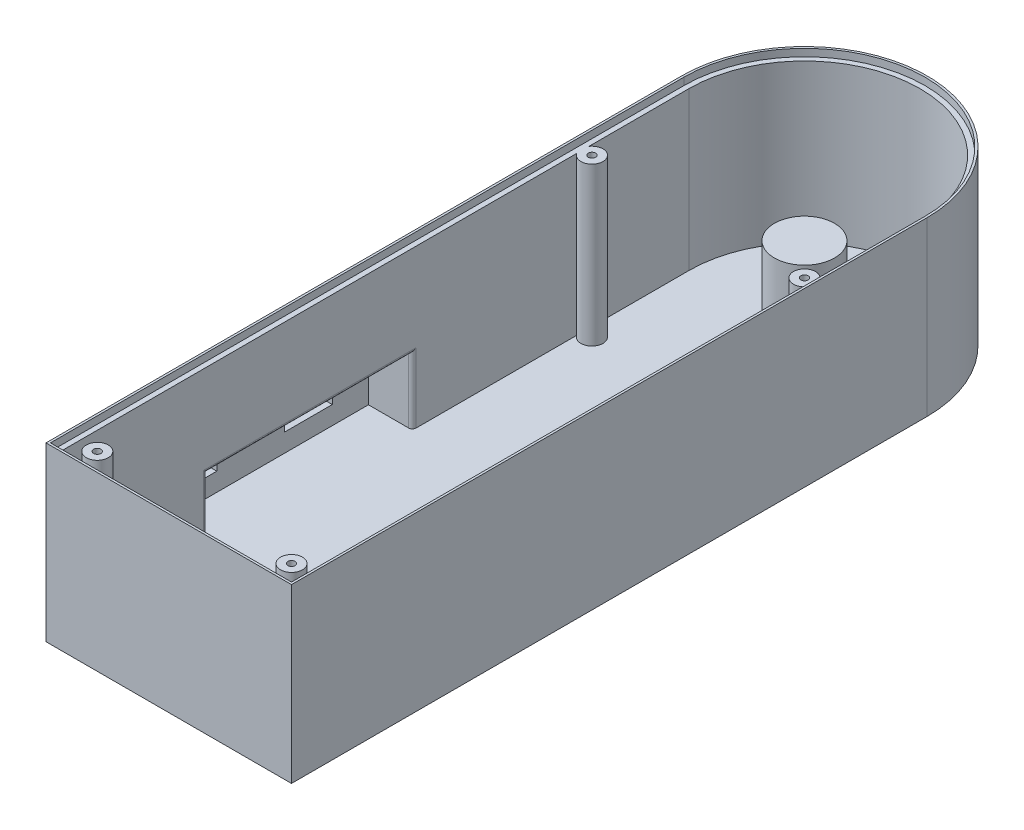
SolidWorks part; units mm, degrees
ref_plane "Front Plane" through (0, 0, 0) normal (0, 0, 1) x (1, 0, 0)
ref_plane "Top Plane" through (0, 0, 0) normal (0, 1, 0) x (1, 0, 0)
ref_plane "Right Plane" through (0, 0, 0) normal (1, 0, 0) x (0, 0, -1)
sketch "Sketch1" plane through (0, 0, 0) normal (0, 0, 1) x (1, 0, 0)
  line L6 (0, 0) -> (0, 47) construction
  line L8 (-31.5, 48) -> (-31.5, 50)
  line L9 (-31.5, 50) -> (-33.5, 50)
  line L10 (-33.5, 50) -> (-33.5, 0)
  line L11 (-33.5, 0) -> (0, 0)
  line L13 (0, 24.8) -> (-8.2, 24.8)
  line L14 (-31.5, 2) -> (-8.2, 2)
  line L17 (-31.5, 45) -> (-31.5, 2)
  line L18 (-8.2, 2) -> (-8.2, 24.8)
  line L19 (0, 0) -> (0, 24.8)
  line L20 (-4, 48) -> (-4, 45)
  line L23 (-31.5, 48) -> (-4, 48)
  line L24 (-31.5, 45) -> (-4, 45)
  dimension "D1" = 33.5
  dimension "D2" = 8
  dimension "D3" = 2
  dimension "D4" = 50
  dimension "D5" = 3
  dimension "D6" = 8.2
  dimension "D7" = 2
  dimension "D8" = 2
  dimension "D9" = 24.8
revolve "Revolve1" add sketch "Sketch1" angle 360 about L6
sketch "Sketch4" plane through (0, 0, 0) normal (0, 0, 1) x (1, 0, 0)
  line L3 (33.5, 0) -> (-33.5, 0)
  line L4 (-31.5, 45) -> (-31.5, 2)
  line L5 (-31.5, 2) -> (31.5, 2)
  line L6 (31.5, 2) -> (31.5, 45)
  line L7 (31.5, 45) -> (-31.5, 45)
  line L8 (31.5, 48) -> (33.5, 48)
  line L9 (-31.5, 48) -> (31.5, 48)
  line L10 (33.5, 48) -> (33.5, 0)
  line L11 (-31.5, 48) -> (-33.5, 48)
  line L12 (-33.5, 48) -> (-33.5, 0)
  dimension "D4" = 2
extrude "Boss-Extrude2" add sketch "Sketch4" along normal blind 173.5
sketch "Sketch6" plane through (0, 48, 0) normal (0, 1, 0) x (1, 0, 0)
  line L0 (4, 0) -> (-4, 0) construction
  circle A0 centre (0, 0) radius 4
extrude "Cut-Extrude1" cut sketch "Sketch6" against normal blind 3
sketch "Sketch9" plane through (0, 0, 173.5) normal (0, 0, 1) x (1, 0, 0)
  line L0 (-31.5, 45) -> (-31.5, 2)
  line L1 (-31.5, 2) -> (31.5, 2)
  line L2 (31.5, 2) -> (31.5, 45)
  line L3 (31.5, 45) -> (-31.5, 45)
extrude "Cut-Extrude2" cut sketch "Sketch9" against normal blind 173.5
sketch "Sketch10" plane through (0, 2, 0) normal (0, 1, 0) x (1, 0, 0)
  line L0 (-8.2, 0) -> (8.2, 0) construction
  circle A0 centre (0, 0) radius 8.2
extrude "Boss-Extrude3" add sketch "Sketch10" along normal blind 22.8
sketch "Sketch11" plane through (0, 0, 173.5) normal (0, 0, 1) x (1, 0, 0)
  line L1 (-31.5, 2) -> (31.5, 2)
  line L2 (-31.5, 2) -> (-31.5, 45)
  line L3 (-31.5, 45) -> (31.5, 45)
  line L4 (31.5, 2) -> (31.5, 45)
extrude "Boss-Extrude4" add sketch "Sketch11" against normal blind 2
sketch "Sketch13" plane through (0, 2, 0) normal (0, 1, 0) x (1, 0, 0)
  line L0 (-26.5, -161.5) -> (-26.5, -171.5)
  line L1 (-31.5, -171.5) -> (-21.5, -171.5)
  line L2 (-31.5, -171.5) -> (-31.5, -161.5)
  line L3 (-31.5, -161.5) -> (-21.5, -161.5)
  line L4 (-21.5, -171.5) -> (-21.5, -161.5)
  line L5 (31.5, -171.5) -> (21.5, -171.5)
  line L6 (31.5, -171.5) -> (31.5, -161.5)
  line L7 (31.5, -161.5) -> (21.5, -161.5)
  line L8 (21.5, -171.5) -> (21.5, -161.5)
  line L9 (-26.5, -171.5) -> (-21.5, -166.5)
  line L10 (-21.5, -166.5) -> (-31.5, -166.5)
  line L11 (26.5, -161.5) -> (26.5, -171.5)
  line L12 (26.5, -171.5) -> (21.5, -166.5)
  line L13 (21.5, -166.5) -> (31.5, -166.5)
  circle A0 centre (-26.5, -166.5) radius 3
  circle A1 centre (26.5, -166.5) radius 3
  dimension "D1" = 10
  dimension "D2" = 10
  dimension "D3" = 10
extrude "Boss-Extrude5" add sketch "Sketch13" along normal blind 43 contours A0 | A1
sketch "Sketch14" plane through (0, 2, 0) normal (0, 1, 0) x (1, 0, 0)
  circle A0 centre (-26.5, -166.5) radius 1
  circle A1 centre (26.5, -166.5) radius 1
extrude "Cut-Extrude3" cut sketch "Sketch14" along normal blind 46
sketch "Sketch15" plane through (0, 48, 0) normal (0, 1, 0) x (1, 0, 0)
  circle A0 centre (-26.5, -166.5) radius 4.3
  circle A1 centre (26.5, -166.5) radius 4.3
extrude "Cut-Extrude4" cut sketch "Sketch15" against normal blind 2
fillet "Fillet1" radius 1 2 edges at (26.5, 46, 170.8) (-26.5, 46, 170.8)
sketch "Sketch16" plane through (0, 48, 0) normal (0, 1, 0) x (1, 0, 0)
  line L0 (0, -173.5) -> (0, -33.5)
  line L1 (33.5, -173.5) -> (-33.5, -173.5) construction
  line L2 (0, -103.5) -> (-33.5, -103.5)
  line L3 (-33.5, -173.5) -> (-33.5, 0) construction
  line L4 (0, -103.5) -> (0, -150.5)
  line L5 (-29.9, -148.5) -> (-3.6, -148.5)
  line L6 (-29.9, -148.5) -> (-29.9, -58.5)
  line L7 (-29.9, -58.5) -> (-3.6, -58.5)
  line L8 (-3.6, -148.5) -> (-3.6, -58.5)
  line L9 (-29.9, -148.5) -> (-3.6, -58.5) construction
  line L10 (-29.9, -58.5) -> (-3.6, -148.5) construction
  line L11 (0, -150.5) -> (-33.5, -150.5)
  line L12 (-33.5, -150.5) -> (-33.5, -56.5)
  line L13 (-33.5, -56.5) -> (0, -56.5)
  line L14 (0, -56.5) -> (0, -103.5)
  arc A0 (-33.5, 0) -> (33.5, 0) centre (0, 0) ccw construction
  point P11 (-16.75, -103.5)
  dimension "D1" = 90
  dimension "D2" = 26.3
  dimension "D3" = 2
  dimension "D4" = 2
sketch "Sketch19" plane through (0, 48, 0) normal (0, 1, 0) x (1, 0, 0)
  line L0 (0, -173.5) -> (0, -33.5) construction
  line L1 (0, -173.5) -> (0, -33.5)
  line L2 (0, -103.5) -> (33.5, -103.5)
  line L3 (33.5, -173.5) -> (33.5, 0) construction
  line L4 (33.5, -103.5) -> (16.75, -103.5)
  line L5 (16.75, -103.5) -> (16.75, -68.5)
  line L7 (16.75, -68.5) -> (16.75, -33.5)
  line L8 (0, -68.5) -> (33.5, -68.5)
  line L9 (0, -138.5) -> (33.5, -138.5)
  line L10 (16.75, -103.5) -> (16.75, -138.5)
  line L11 (16.75, -138.5) -> (16.75, -173.5)
  line L12 (33.5, -173.5) -> (-33.5, -173.5) construction
  circle A0 centre (16.75, -51) radius 6
  circle A1 centre (16.75, -86) radius 6
  circle A2 centre (16.75, -121) radius 6
  circle A3 centre (16.75, -156) radius 6
extrude "Cut-Extrude5" cut sketch "Sketch19" against normal blind 3 contours A0 | A1 | A2 | A3
ref_plane "Plane2" through (0, 0, 56.5) normal (0, 0, 1) x (1, 0, 0)
sketch "Sketch20" plane through (0, 0, 56.5) normal (0, 0, 1) x (1, 0, 0)
  line L0 (9, 48) -> (-11.2073, 83)
  line L1 (0, 48) -> (-33.5, 48) construction
  line L3 (-33.5, 48) -> (9, 48)
  line L5 (5.5359, 50) -> (-12.362, 81)
  line L7 (-31.5, 50) -> (5.5359, 50)
  line L8 (-33.5, 48) -> (-33.5, 0) construction
  line L11 (-33.5, 48) -> (-33.5, 83)
  line L12 (-33.5, 83) -> (-11.2073, 83)
  line L13 (-31.5, 50) -> (-31.5, 81)
  line L14 (-31.5, 81) -> (-12.362, 81)
  dimension "D1" = 60
  dimension "D3" = 2
  dimension "D4" = 2
  dimension "D2" = 2
  dimension "D5" = 2
  dimension "D6" = 9
  dimension "D7" = 35
extrude "Boss-Extrude6" add sketch "Sketch20" along normal up to vertex (94 mm away) up to point (-33.5, 48, 150.5)
sketch "Sketch21" plane through (0, 50, 0) normal (0, 1, 0) x (1, 0, 0)
  line L1 (-31.5, -150.5) -> (5.5359, -150.5)
  line L2 (-31.5, -150.5) -> (-31.5, -56.5)
  line L3 (-31.5, -56.5) -> (5.5359, -56.5)
  line L4 (5.5359, -150.5) -> (5.5359, -56.5)
extrude "Cut-Extrude6" cut sketch "Sketch21" against normal blind 13
fillet "Fillet2" radius 1 2 edges at (-11.2073, 83, 103.5) (-33.5, 83, 103.5)
sketch "Sketch22" plane through (0, 0, 150.5) normal (0, 0, 1) x (1, 0, 0)
  line L1 (-33.5, 48) -> (-33.5, 45)
  line L2 (-33.5, 45) -> (9, 45)
  line L3 (9, 45) -> (9, 48)
  line L7 (9, 48) -> (-10.9186, 82.5)
  line L8 (-11.7846, 83) -> (-32.5, 83)
  line L9 (-33.5, 48) -> (-31.5, 48)
  line L10 (-11.7846, 83) -> (-32.5, 83)
  line L11 (-12.362, 81) -> (5.5359, 50)
  line L12 (5.5359, 50) -> (5.5359, 48)
  line L13 (5.5359, 48) -> (9, 48)
  line L14 (9, 48) -> (-10.9186, 82.5)
  line L27 (-33.5, 82) -> (-33.5, 48)
  line L28 (-33.5, 82) -> (-33.5, 48)
  line L29 (-31.5, 48) -> (-31.5, 81)
  line L31 (-31.5, 81) -> (-12.362, 81)
  arc A2 (-10.9186, 82.5) -> (-11.7846, 83) centre (-11.7846, 82) ccw
  arc A3 (-10.9186, 82.5) -> (-11.7846, 83) centre (-11.7846, 82) ccw
  arc A5 (-32.5, 83) -> (-33.5, 82) centre (-32.5, 82) ccw
  arc A6 (-32.5, 83) -> (-33.5, 82) centre (-32.5, 82) ccw
  dimension "D2" = 3
  dimension "D1" = 0
extrude "Boss-Extrude8" add sketch "Sketch22" against normal blind 2
sketch "Sketch23" plane through (27.5346, 15.8971, 0) normal (0.866, 0.5, 0) x (0, 0, -1)
  line L0 (-56.5, 37.0692) -> (-56.5, 76.9064) construction
  line L1 (-150.5, 37.0692) -> (-56.5, 37.0692)
  line L2 (-150.5, 37.0692) -> (-150.5, 67.8692)
  line L3 (-150.5, 67.8692) -> (-56.5, 67.8692)
  line L4 (-56.5, 37.0692) -> (-56.5, 67.8692)
  line L5 (-103.5, 41.5692) -> (-103.5, 67.8692)
  line L6 (-103.5, 67.8692) -> (-56.5, 52.4692)
  line L7 (-56.5, 52.4692) -> (-150.5, 52.4692)
  line L9 (-139.75, 42.0692) -> (-67.25, 42.0692)
  line L10 (-139.75, 42.0692) -> (-139.75, 67.3692)
  line L11 (-139.75, 67.3692) -> (-67.25, 67.3692)
  line L12 (-67.25, 42.0692) -> (-67.25, 67.3692)
  line L13 (-139.75, 42.0692) -> (-67.25, 67.3692) construction
  line L14 (-139.75, 67.3692) -> (-67.25, 42.0692) construction
  point P12 (-103.5, 54.7192)
  dimension "D1" = 94
  dimension "D2" = 72.5
  dimension "D3" = 5
  dimension "D4" = 25.3
extrude "Cut-Extrude7" cut sketch "Sketch23" against normal blind 2 contours L11 L12 L9 L10
sketch "Sketch24" plane through (0, 0, 56.5) normal (0, 0, -1) x (-1, 0, 0)
  line L12 (-9, 48) -> (-9, 45)
  line L13 (-9, 45) -> (33.5, 45)
  line L14 (33.5, 45) -> (33.5, 82)
  line L15 (32.5, 83) -> (11.7846, 83)
  line L16 (10.9186, 82.5) -> (-9, 48)
  arc A2 (33.5, 82) -> (32.5, 83) centre (32.5, 82) ccw
  arc A3 (11.7846, 83) -> (10.9186, 82.5) centre (11.7846, 82) ccw
extrude "Boss-Extrude9" add sketch "Sketch24" against normal blind 2
sketch "Sketch25" plane through (0, 48, 0) normal (0, 1, 0) x (1, 0, 0)
  line L0 (0, -173.5) -> (0, -33.5) construction
  line L1 (0, -173.5) -> (0, -33.5) construction
  line L2 (0, -33.5) -> (33.5, -33.5) construction
  line L3 (33.5, -173.5) -> (33.5, 0) construction
  line L4 (0, -33.5) -> (-33.5, -33.5) construction
  line L5 (-33.5, -56.5) -> (-33.5, 0) construction
  line L7 (-33.5, -33.5) -> (-24.5, -33.5) construction
  line L8 (-33.5, -33.5) -> (-33.5, -24.5) construction
  line L9 (-33.5, -24.5) -> (-24.5, -24.5) construction
  line L10 (-24.5, -33.5) -> (-24.5, -24.5) construction
  line L11 (33.5, -33.5) -> (24.5, -33.5) construction
  line L12 (33.5, -33.5) -> (33.5, -24.5) construction
  line L13 (33.5, -24.5) -> (24.5, -24.5) construction
  line L14 (24.5, -33.5) -> (24.5, -24.5) construction
  circle A0 centre (29, -29) radius 3
  circle A1 centre (-29, -29) radius 3
  dimension "D4" = 4.5
  dimension "D6" = 6
  dimension "D1" = 9
  dimension "D2" = 9
  dimension "D3" = 9
  dimension "D5" = 4.5
  dimension "D7" = 4.5
extrude "Boss-Extrude10" add sketch "Sketch25" against normal blind 48
sketch "Sketch26" plane through (0, 48, 0) normal (0, 1, 0) x (1, 0, 0)
  circle A0 centre (29, -29) radius 1
  circle A1 centre (-29, -29) radius 1
  dimension "D1" = 2
extrude "Cut-Extrude8" cut sketch "Sketch26" against normal blind 46
sketch "Sketch27" plane through (0, 48, 0) normal (0, 1, 0) x (1, 0, 0)
  circle A0 centre (-29, -29) radius 4.3
  circle A1 centre (29, -29) radius 4.3
  dimension "D1" = 8.6
extrude "Cut-Extrude9" cut sketch "Sketch27" against normal blind 2
fillet "Fillet3" radius 1 2 edges at (29, 46, 33.3) (-29, 46, 33.3)
sketch "Sketch29" plane through (-33.5, 0, 0) normal (-1, 0, 0) x (0, 0, 1)
  line L0 (103.5, 82) -> (103.5, 0)
  line L2 (173.5, 0) -> (0, 0) construction
  line L3 (73.5, 22) -> (73.5, 0)
  line L4 (73.5, 22) -> (133.5, 22)
  line L5 (73.5, 0) -> (133.5, 0)
  line L6 (133.5, 22) -> (133.5, 0)
  line L7 (73.5, 22) -> (133.5, 0) construction
  line L8 (73.5, 0) -> (133.5, 22) construction
  line L9 (75.5, 20) -> (75.5, 2)
  line L10 (75.5, 20) -> (131.5, 20)
  line L11 (75.5, 2) -> (131.5, 2)
  line L12 (131.5, 20) -> (131.5, 2)
  line L13 (75.5, 20) -> (131.5, 2) construction
  line L14 (75.5, 2) -> (131.5, 20) construction
  line L15 (150.5, 82) -> (56.5, 82) construction
  point P7 (103.5, 11)
  point P8 (103.5, 11)
  dimension "D1" = 22
  dimension "D2" = 60
  dimension "D3" = 0
  dimension "D4" = 2
  dimension "D5" = 2
  dimension "D6" = 2
  dimension "D7" = 2
  dimension "D8" = 0
sketch "Sketch30" plane through (-33.5, 0, 0) normal (-1, 0, 0) x (0, 0, 1)
  line L0 (75.5, 20) -> (75.5, 2) construction
  line L1 (75.5, 20) -> (131.5, 20) construction
  line L2 (75.5, 2) -> (131.5, 2) construction
  line L3 (131.5, 20) -> (131.5, 2) construction
  line L4 (131.5, 20) -> (131.5, 2)
  line L5 (75.5, 2) -> (131.5, 2)
  line L6 (75.5, 20) -> (75.5, 2)
  line L7 (75.5, 20) -> (131.5, 20)
extrude "Cut-Extrude10" cut sketch "Sketch30" against normal blind 2
sketch "Sketch31" plane through (-33.5, 0, 0) normal (-1, 0, 0) x (0, 0, 1)
  line L0 (131.5, 20) -> (131.5, 2) construction
  line L1 (133.5, 22) -> (133.5, 0) construction
  line L2 (75.5, 2) -> (131.5, 2) construction
  line L3 (73.5, 0) -> (133.5, 0) construction
  line L4 (75.5, 20) -> (75.5, 2) construction
  line L5 (75.5, 20) -> (131.5, 20) construction
  line L6 (73.5, 22) -> (73.5, 0) construction
  line L7 (73.5, 22) -> (133.5, 22) construction
  line L8 (131.5, 20) -> (131.5, 2)
  line L9 (133.5, 22) -> (133.5, 0)
  line L10 (75.5, 2) -> (131.5, 2)
  line L11 (73.5, 0) -> (133.5, 0)
  line L12 (75.5, 20) -> (75.5, 2)
  line L13 (75.5, 20) -> (131.5, 20)
  line L14 (73.5, 22) -> (73.5, 0)
  line L15 (73.5, 22) -> (133.5, 22)
extrude "Boss-Extrude11" add sketch "Sketch31" along normal blind 12
fillet "Fillet4" radius 1 3 edges at (-33.5, 11, 133.5) (-33.5, 22, 103.5) (-33.5, 11, 73.5)
sketch "Sketch33" plane through (-45.5, 0, 0) normal (-1, 0, 0) x (0, 0, 1)
  line L0 (131.5, 2) -> (131.5, 20) construction
  line L1 (75.5, 2) -> (131.5, 2) construction
  line L2 (75.5, 20) -> (75.5, 2) construction
  line L3 (131.5, 20) -> (75.5, 20) construction
  line L4 (131.5, 2) -> (131.5, 20)
  line L5 (75.5, 2) -> (131.5, 2)
  line L6 (75.5, 20) -> (75.5, 2)
  line L7 (131.5, 20) -> (75.5, 20)
extrude "Boss-Extrude12" add sketch "Sketch33" against normal blind 2
sketch "Sketch34" plane through (-88.691, 83, 0) normal (0, -1, 0) x (0, 0, -1)
  line L0 (-139.75, 73.9064) -> (-67.25, 73.9064) construction
  line L2 (-150.5, 76.9064) -> (-56.5, 76.9064) construction
  text T0 "I.Hand" font "Century Gothic" height 14
  dimension "D1" = 3
  dimension "D2" = 0
  dimension "D3" = 0
extrude "Cut-Extrude11" cut sketch "Sketch34" along normal blind 1
sketch "Sketch35" plane through (-45.5, 0, 0) normal (-1, 0, 0) x (0, 0, 1)
  line L1 (75.5, 2) -> (131.5, 2) construction
  line L2 (75.5, 2) -> (75.5, 20) construction
  line L3 (75.5, 20) -> (131.5, 20) construction
  line L4 (131.5, 2) -> (131.5, 20) construction
  line L5 (75.5, 2) -> (131.5, 20) construction
  line L6 (75.5, 20) -> (131.5, 2) construction
  line L7 (133.5, 22) -> (73.5, 22) construction
  line L8 (73.5, 0) -> (133.5, 0) construction
  line L9 (73.5, 22) -> (73.5, 0) construction
  line L10 (133.5, 0) -> (133.5, 22) construction
  line L11 (76.725, 7) -> (85.375, 7) construction
  line L13 (85.375, 7) -> (85.375, 19)
  line L14 (85.375, 19) -> (98.475, 19)
  line L15 (98.475, 19) -> (98.475, 7)
  line L16 (116.875, 7) -> (116.875, 18.8)
  line L17 (116.875, 18.8) -> (126.775, 18.8)
  line L18 (126.775, 18.8) -> (126.775, 7)
  line L19 (76.725, 7) -> (130.275, 7) construction
  line L20 (116.875, 7) -> (126.775, 7)
  line L21 (85.375, 7) -> (98.475, 7)
  point P0 (103.5, 11)
  point P24 (103.5, 7)
  dimension "D1" = 2
  dimension "D2" = 2
  dimension "D3" = 2
  dimension "D4" = 2
  dimension "D5" = 12
  dimension "D6" = 13.1
  dimension "D7" = 18.4
  dimension "D8" = 9.9
  dimension "D9" = 11.8
  dimension "D10" = 8.65
  dimension "D11" = 3.5
  dimension "D12" = 5
extrude "Cut-Extrude12" cut sketch "Sketch35" against normal blind 2
fillet "Fillet5" radius 1 3 edges at (-45.5, 11, 133.5) (-45.5, 11, 73.5) (-45.5, 22, 103.5)
sketch "Sketch36" plane through (0, 48, 0) normal (0, 1, 0) x (1, 0, 0)
  line L0 (0, -33.5) -> (0, -34.8932)
  line L1 (0, -34.8932) -> (0, -38.8932)
  line L2 (20.5725, -33.5) -> (20.5725, -28.2088)
  line L3 (-20.5725, -28.2088) -> (-20.5725, -33.5)
  arc A0 (-33.5, 0) -> (33.5, 0) centre (0, 0) ccw construction
  arc A1 (0, -34.8932) -> (-20.5725, -28.2088) centre (0, 0.1068) cw
  arc A2 (0, -34.8932) -> (20.5725, -28.2088) centre (0, 0.1068) ccw
  arc A3 (0, -38.8932) -> (-20.5725, -33.5) centre (0, 3.0408) cw
  arc A4 (0, -38.8932) -> (20.5725, -33.5) centre (0, 3.0408) ccw
  dimension "D1" = 5.2912
extrude "Cut-Extrude13" cut sketch "Sketch36" against normal blind 3 and the other way through all contours L1 A4 L2 A2 | A3 L1 A1 L3 region at (10.7626, 48, 34.8016) region at (-10.7626, 48, 34.8016)
fillet "Fillet6" radius 1 3 edges at (-31.5, 11, 75.5) (-31.5, 20, 103.5) (-31.5, 11, 131.5)
sketch "Sketch37" plane through (31.5, 0, 0) normal (-1, 0, 0) x (0, 0, 1)
  line L0 (30.6583, 33.5) -> (171.5, 33.5)
  line L1 (30.6583, 2) -> (30.6583, 45) construction
  line L2 (171.5, 2) -> (171.5, 45) construction
  line L3 (171.5, 45) -> (30.6583, 45) construction
  line L5 (30.6583, 33.5) -> (171.5, 33.5)
  line L6 (30.6583, 33.5) -> (30.6583, 31.4)
  line L7 (30.6583, 31.4) -> (171.5, 31.4)
  line L8 (171.5, 33.5) -> (171.5, 31.4)
  line L9 (30.6583, 35.5) -> (171.5, 35.5)
  line L10 (30.6583, 35.5) -> (30.6583, 29.4)
  line L11 (30.6583, 29.4) -> (171.5, 29.4)
  line L12 (171.5, 35.5) -> (171.5, 29.4)
  line M3 (30.6583, 45) -> (30.6583, 2)
  line M5 (171.5, 2) -> (171.5, 45)
  dimension "D1" = 11.5
  dimension "D2" = 2.1
  dimension "D3" = 2
  dimension "D4" = 2
extrude "Boss-Extrude13" add sketch "Sketch37" along normal blind 4 contours L9 L0 M3 M5 | L11 L7 M3 M5 region at (31.5, 34.5, 101.0792) region at (31.5, 30.4, 101.0792)
fillet "Fillet8" radius 2 1 edges at (31.5, 29.4, 101.0792)
ref_plane "Plane4" through (0, 45, 0) normal (0, -1, 0) x (-1, 0, 0)
sketch "Sketch38" plane through (0, 45, 0) normal (0, -1, 0) x (-1, 0, 0)
  line L1 (-46.829, 40.8309) -> (54.6886, 40.8309)
  line L2 (-46.829, 40.8309) -> (-46.829, -197.7454)
  line L3 (-46.829, -197.7454) -> (54.6886, -197.7454)
  line L4 (54.6886, 40.8309) -> (54.6886, -197.7454)
extrude "Cut-Extrude14" cut sketch "Sketch38" against normal blind 100
sketch "Sketch39" plane through (0, 45, 0) normal (0, 1, 0) x (1, 0, 0)
  line L0 (33.5, 0) -> (33.5, -173.5) construction
  line L1 (33.5, -173.5) -> (-33.5, -173.5) construction
  line L2 (-33.5, -173.5) -> (-33.5, 0) construction
  line L3 (33.5, 0) -> (33.5, -173.5)
  line L4 (33.5, -173.5) -> (-33.5, -173.5)
  line L5 (-33.5, -173.5) -> (-33.5, 0)
  line L6 (-32.9, -172.9) -> (-32.9, 0)
  line L7 (32.9, 0) -> (32.9, -172.9)
  line L8 (32.9, -172.9) -> (-32.9, -172.9)
  arc A0 (33.5, 0) -> (-33.5, 0) centre (0, 0) ccw construction
  arc A1 (33.5, 0) -> (-33.5, 0) centre (0, 0) ccw
  arc A2 (32.9, 0) -> (-32.9, 0) centre (0, 0) ccw
  dimension "D1" = 0.6
extrude "Boss-Extrude14" add sketch "Sketch39" along normal blind 2
